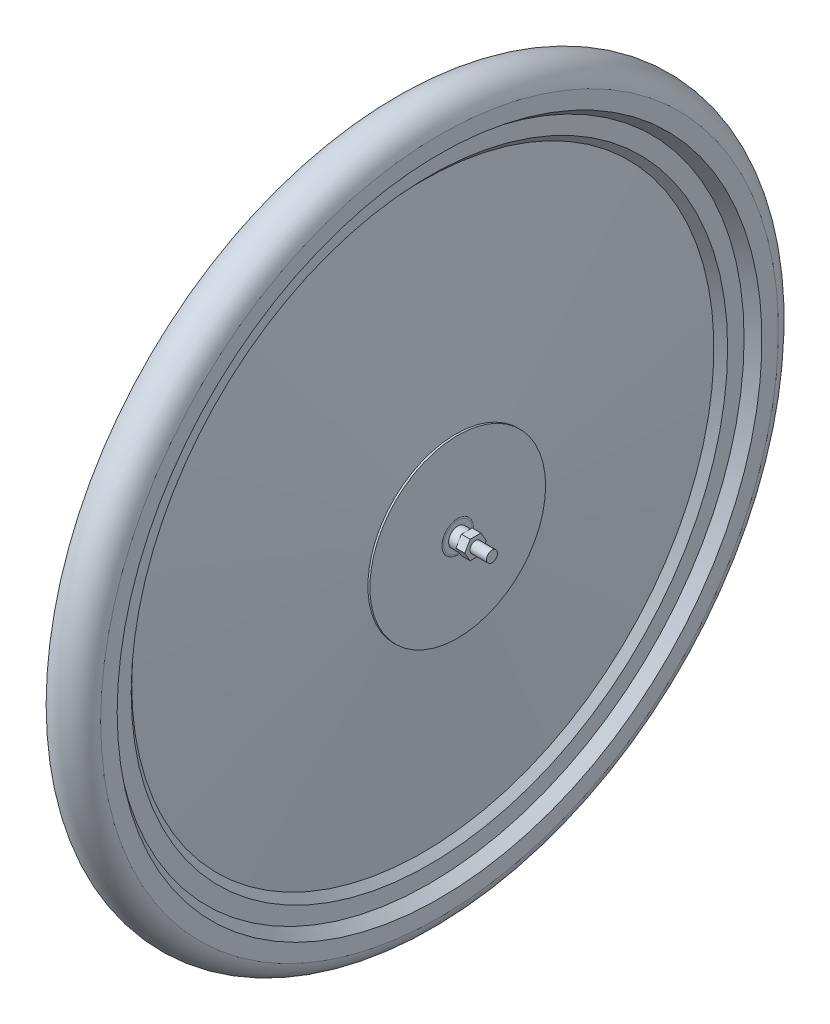
SolidWorks part; units mm, degrees
ref_plane "Front Plane" through (0, 0, 0) normal (0, 0, 1) x (1, 0, 0)
ref_plane "Top Plane" through (0, 0, 0) normal (0, 1, 0) x (1, 0, 0)
ref_plane "Right Plane" through (0, 0, 0) normal (1, 0, 0) x (0, 0, -1)
sketch "Sketch1" plane through (0, 0, 0) normal (1, 0, 0) x (0, 0, -1)
  circle A0 centre (0, 0) radius 17.5
  dimension "D1" = 35
extrude "Boss-Extrude1" add sketch "Sketch1" along normal mid plane 78
fillet "Fillet1" radius 4.5 2 edges at (-39, 0, -17.5) (39, 0, -17.5)
sketch "Sketch2" plane through (0, 0, 0) normal (1, 0, 0) x (0, 0, -1)
  circle A0 centre (0, 0) radius 5
  dimension "D1" = 10
extrude "Boss-Extrude2" add sketch "Sketch2" along normal mid plane 140
sketch "Sketch6" plane through (0, 0, 0) normal (0, 0, 1) x (1, 0, 0)
  line L0 (0, 0) -> (0, 26) construction
  line L1 (0, 0) -> (0, 265) construction
  line L2 (-31.1195, 0) -> (31.1195, 0)
  line L3 (-31.1195, 0) -> (-31.1195, 26)
  line L4 (-31.1195, 26) -> (31.1195, 26)
  line L5 (31.1195, 0) -> (31.1195, 26)
  line L6 (-31.1195, 0) -> (31.1195, 26) construction
  line L7 (-31.1195, 26) -> (31.1195, 0) construction
  line L8 (0, 0) -> (0, 271.5) construction
  line L9 (-7, 0) -> (7, 0)
  line L10 (-7, 0) -> (-7, 265)
  line L11 (-7, 265) -> (7, 265)
  line L12 (7, 0) -> (7, 265)
  line L13 (-7, 0) -> (7, 265) construction
  line L14 (-7, 265) -> (7, 0) construction
  line L15 (-31.1195, 26) -> (-7, 265)
  line L16 (-13, 0) -> (13, 0)
  line L17 (-13, 0) -> (-13, 271.5)
  line L18 (-13, 271.5) -> (13, 271.5)
  line L19 (13, 0) -> (13, 271.5)
  line L20 (-13, 0) -> (13, 271.5) construction
  line L21 (-13, 271.5) -> (13, 0) construction
  line L22 (31.1195, 26) -> (7, 265)
  line L23 (0, 0) -> (0, 286.5) construction
  line L24 (-7, 265) -> (-13, 271.5)
  line L25 (-13, 0) -> (13, 0)
  line L26 (-13, 0) -> (-13, 286.5)
  line L27 (-13, 286.5) -> (13, 286.5)
  line L28 (13, 0) -> (13, 286.5)
  line L29 (-13, 0) -> (13, 286.5) construction
  line L30 (-13, 286.5) -> (13, 0) construction
  line L31 (7, 265) -> (13, 271.5)
  point P3 (0, 13)
  point P8 (0, 132.5)
  point P14 (0, 135.75)
  point P22 (0, 143.25)
  dimension "D1" = 26
  dimension "D2" = 265
  dimension "D3" = 14
  dimension "D4" = 6.5
  dimension "D5" = 15
  dimension "D6" = 26
revolve "Revolve1" add sketch "Sketch6" angle 360 about L2 region at (-22.0597, 13, 0) region at (-10, 13, 0) region at (-19.0398, 85.8486, 0) region at (0, 13, 0) region at (-9.858, 131.3403, 0) region at (10, 13, 0) region at (0, 145.5, 0) region at (0, 268.575, 0) region at (0, 279, 0) region at (22.0597, 13, 0) region at (9.858, 131.3403, 0) region at (19.0398, 85.8486, 0)
sketch "Sketch7" plane through (0, 0, 0) normal (0, 0, 1) x (1, 0, 0)
  line L0 (13, 286.5) -> (-13, 286.5) construction
  line L1 (13, 286.5) -> (-13, 286.5)
  line L2 (0, 286.5) -> (0, 326.5) construction
  line L3 (-22.25, 308.5) -> (22.25, 308.5) construction
  line L4 (-22.25, 293.5) -> (-13, 286.5)
  line L5 (-22.25, 308.5) -> (22.25, 308.5)
  line L6 (-22.25, 308.5) -> (-22.25, 293.5)
  line L7 (-22.25, 293.5) -> (22.25, 293.5)
  line L8 (22.25, 308.5) -> (22.25, 293.5)
  line L9 (22.25, 293.5) -> (13, 286.5)
  arc A0 (-22.25, 308.5) -> (22.25, 308.5) centre (0, 303.7483) cw
  point P8 (0, 326.5)
  dimension "D1" = 40
  dimension "D2" = 44.5
  dimension "D3" = 18
  dimension "D4" = 15
revolve "Revolve2" add sketch "Sketch7" angle 360 about L2 region at (0, 290.3061, 0) region at (0, 301, 0) region at (0, 316.0186, 0)
sketch "Sketch8" plane through (0, 0, 0) normal (1, 0, 0) x (0, 0, -1)
  circle A0 centre (0, 0) radius 28.3
  dimension "D1" = 56.6
extrude "Boss-Extrude5" add sketch "Sketch8" against normal blind 6.5 from offset 37
sketch "Sketch9" plane through (37, 0, 0) normal (1, 0, 0) x (0, 0, -1)
  circle A0 centre (0, 0) radius 80
  dimension "D1" = 160
extrude "Boss-Extrude6" add sketch "Sketch9" along normal blind 1.8
sketch "Sketch10" plane through (39, 0, 0) normal (1, 0, 0) x (0, 0, -1)
  line L1 (9.815, 0) -> (4.9075, 8.5)
  line L2 (4.9075, 8.5) -> (-4.9075, 8.5)
  line L3 (-4.9075, 8.5) -> (-9.815, 0)
  line L4 (-9.815, 0) -> (-4.9075, -8.5)
  line L5 (-4.9075, -8.5) -> (4.9075, -8.5)
  line L6 (4.9075, -8.5) -> (9.815, 0)
  circle A0 centre (0, 0) radius 8.5 construction
  circle A1 centre (0, 0) radius 8.5
  circle M3 centre (0, 0) radius 5
  dimension "D1" = 17
extrude "Boss-Extrude7" add sketch "Sketch10" along normal blind 8 contours A1 M3 region at (39, 2.1377, -7.9781)
extrude "Boss-Extrude8" add sketch "Sketch10<3>" along normal blind 8 from surface contours A1 M3 | A1 L2 L3 | A1 L3 L4 | A1 L4 L5 | A1 L5 L6 | A1 L6 L1 | A1 L1 L2 | A1 region at (39, 0, -8.7853) region at (39, 7.6083, -4.3926) region at (39, 2.1377, -7.9781) region at (39, -7.6083, -4.3926) region at (39, 7.6083, 4.3926) region at (39, -7.6083, 4.3926) region at (39, 0, 8.7853) starting at face at (47, 0, -5)
sketch "Sketch10<3>" plane through (39, 0, 0) normal (1, 0, 0) x (0, 0, -1) same geometry as "Sketch10"
mirror "Mirror2" about plane through (0, 0, 0) normal (1, 0, 0) of "Boss-Extrude7", "Boss-Extrude8"
